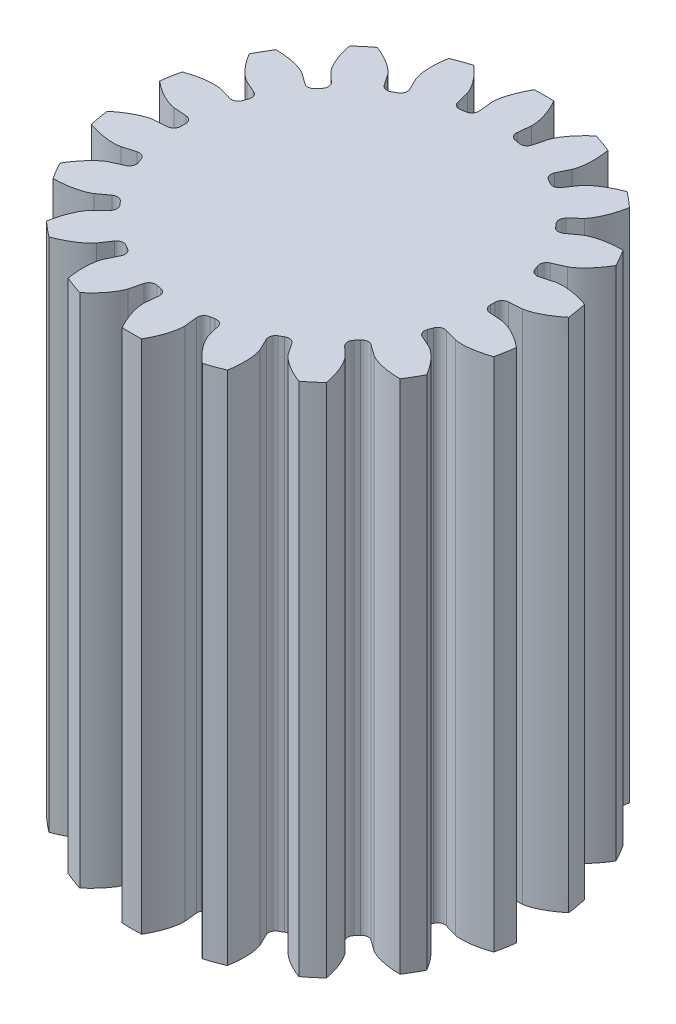
SolidWorks part; units mm, degrees
ref_plane "Front Plane" through (0, 0, 0) normal (0, 0, 1) x (1, 0, 0)
ref_plane "Top Plane" through (0, 0, 0) normal (0, 1, 0) x (1, 0, 0)
ref_plane "Right Plane" through (0, 0, 0) normal (1, 0, 0) x (0, 0, -1)
ref_axis "Axis" through (0, -13.75, 0) along (0, 1, 0)
sketch "Sketch1" plane through (0, 0, 0) normal (0, 1, 0) x (1, 0, 0)
  circle A0 centre (0, 0) radius 10
  dimension "D1" = 20
extrude "Gear Boss" add sketch "Sketch1" along normal mid plane 25
sketch "Sketch2" plane through (0, 0, 0) normal (0, 1, 0) x (1, 0, 0)
  line L0 (0, 0) -> (10, 0) construction
  line L1 (8.4425, 0.4988) -> (7.8104, 0.453)
  line L2 (9.9193, 1.2676) -> (9.9193, 0) construction
  line L3 (7.8104, -0.453) -> (8.4425, -0.4988)
  line L4 (8.4425, -0.4988) -> (8.4425, 0.4988) construction
  line L5 (9.9193, 0) -> (9.9193, -1.2676) construction
  circle A0 centre (0, 0) radius 8.4572 construction
  circle A1 centre (0, 0) radius 10 construction
  circle A4 centre (0, 0) radius 10
  arc A5 (7.4991, -0.1133) -> (7.4991, 0.1133) centre (0, 0) ccw
  arc A6 (7.8104, -0.453) -> (7.4991, -0.1133) centre (7.8346, -0.1184) cw
  arc A7 (7.8104, 0.453) -> (7.4991, 0.1133) centre (7.8346, 0.1184) ccw
  spline S0 degree 4 poles (8.4425, 0.4988) (8.445, 0.499) (8.452, 0.4996) (8.4734, 0.5021) (8.5155, 0.509) (8.5672, 0.5201) (8.6262, 0.5355) (8.6828, 0.5523) (8.7311, 0.5679) (8.7789, 0.5846) (8.8264, 0.6022) (8.8836, 0.6248) (8.9519, 0.6536) (9.0311, 0.6897) (9.1202, 0.7335) (9.2101, 0.7811) (9.2979, 0.8305) (9.3857, 0.8832) (9.47, 0.9363) (9.5567, 0.9942) (9.6362, 1.0492) (9.7241, 1.1139) (9.7947, 1.167) (9.8866, 1.2405) (9.9405, 1.2848) (10.0031, 1.3379) (10.0307, 1.3621) (10.0477, 1.3769) knots 0 0 0 0 0 0.005377 0.015084 0.04661 0.092111 0.119476 0.146842 0.174209 0.201575 0.228941 0.256307 0.307035 0.361767 0.4165 0.471232 0.525964 0.580697 0.635429 0.690161 0.744894 0.799626 0.854358 0.909091 0.954545 1 1 1 1 1 construction
  spline S1 degree 4 poles (8.4425, 0.4988) (8.445, 0.499) (8.452, 0.4996) (8.4734, 0.5021) (8.5155, 0.509) (8.5672, 0.5201) (8.6262, 0.5355) (8.6828, 0.5523) (8.7311, 0.5679) (8.7789, 0.5846) (8.8264, 0.6022) (8.8836, 0.6248) (8.9519, 0.6536) (9.0311, 0.6897) (9.1202, 0.7335) (9.2101, 0.7811) (9.2979, 0.8305) (9.3857, 0.8832) (9.47, 0.9363) (9.5567, 0.9942) (9.6362, 1.0492) (9.7241, 1.1139) (9.7947, 1.167) (9.8667, 1.2246) (9.9016, 1.2529) (9.9193, 1.2676) knots 0 0 0 0 0 0.005377 0.015084 0.04661 0.092111 0.119476 0.146842 0.174209 0.201575 0.228941 0.256307 0.307035 0.361767 0.4165 0.471232 0.525964 0.580697 0.635429 0.690161 0.744894 0.799626 0.854358 0.909091 0.909091 0.909091 0.909091 0.909091
  spline S2 degree 4 poles (8.4425, -0.4988) (8.445, -0.499) (8.452, -0.4996) (8.4734, -0.5021) (8.5155, -0.509) (8.5672, -0.5201) (8.6262, -0.5355) (8.6828, -0.5523) (8.7311, -0.5679) (8.7789, -0.5846) (8.8264, -0.6022) (8.8836, -0.6248) (8.9519, -0.6536) (9.0311, -0.6897) (9.1202, -0.7335) (9.2101, -0.7811) (9.2979, -0.8305) (9.3857, -0.8832) (9.47, -0.9363) (9.5567, -0.9942) (9.6362, -1.0492) (9.7241, -1.1139) (9.7947, -1.167) (9.8866, -1.2405) (9.9405, -1.2848) (10.0031, -1.3379) (10.0307, -1.3621) (10.0477, -1.3769) knots 0 0 0 0 0 0.005377 0.015084 0.04661 0.092111 0.119476 0.146842 0.174209 0.201575 0.228941 0.256307 0.307035 0.361767 0.4165 0.471232 0.525964 0.580697 0.635429 0.690161 0.744894 0.799626 0.854358 0.909091 0.954545 1 1 1 1 1 construction
  spline S3 degree 4 poles (8.4425, -0.4988) (8.445, -0.499) (8.452, -0.4996) (8.4734, -0.5021) (8.5155, -0.509) (8.5672, -0.5201) (8.6262, -0.5355) (8.6828, -0.5523) (8.7311, -0.5679) (8.7789, -0.5846) (8.8264, -0.6022) (8.8836, -0.6248) (8.9519, -0.6536) (9.0311, -0.6897) (9.1202, -0.7335) (9.2101, -0.7811) (9.2979, -0.8305) (9.3857, -0.8832) (9.47, -0.9363) (9.5567, -0.9942) (9.6362, -1.0492) (9.7241, -1.1139) (9.7947, -1.167) (9.8667, -1.2246) (9.9016, -1.2529) (9.9193, -1.2676) knots 0 0 0 0 0 0.005377 0.015084 0.04661 0.092111 0.119476 0.146842 0.174209 0.201575 0.228941 0.256307 0.307035 0.361767 0.4165 0.471232 0.525964 0.580697 0.635429 0.690161 0.744894 0.799626 0.854358 0.909091 0.909091 0.909091 0.909091 0.909091
  point P11 (8.439, 0.5553)
  point P19 (9.8851, 1.5118)
  dimension "D1" = 16.9145
  dimension "D3" = 20
  dimension "D6" = 7.5
  dimension "D2" = 0.3355
  dimension "D4" = 8.292
extrude "Tooth Cut" cut sketch "Sketch2" against normal through all both and the other way through all contours S3 S1 region at (9.0027, 0, 0)
pattern_circular "Tooth Pattern" count 18 over 360 about axis through (0, -13.75, 0) along (0, 1, 0) of "Tooth Cut"
equation "\"ringGearToothCount\" = 138"
equation "\"sunGearToothCount\" = 18"
equation "\"planetGearToothCount\" = (\"ringGearToothCount\" - \"sunGearToothCount\") / 2"
equation "\"faceWidth\" = 25mm"
equation "\"module\" = 1"
equation "\"pressureAngle\" = 20deg"
equation "\"toothCount\"= \"sunGearToothCount\""
equation "\"pitchAngle\" = 360deg / \"toothCount\""
equation "\"pitchDiameter\" = \"module\" * \"toothCount\""
equation "\"pitchRadius\" = \"pitchDiameter\" / 2"
equation "\"baseDiameter\" = \"pitchDiameter\" * cos(\"pressureAngle\")"
equation "\"baseRadius\" = \"baseDiameter\" / 2"
equation "\"addendum\" = 1.0 * \"module\""
equation "\"dedendum\" = 1.25 * \"module\""
equation "\"rootClearance\" = 0.25 * \"module\""
equation "\"addendumDiameter\" = \"pitchDiameter\" + 2 * \"addendum\""
equation "\"addendumRadius\" = \"addendumDiameter\" / 2"
equation "\"dedendumDiameter\" = \"pitchDiameter\" - 2 * \"dedendum\""
equation "\"dedendumRadius\" = \"dedendumDiameter\" / 2"
equation "\"rootDiameter\" = \"dedendumDiameter\" - 2 * \"rootClearance\""
equation "\"rootRadius\" = \"rootDiameter\" / 2"
equation "\"dedendumFilletRadius\" = \"rootClearance\" * cos(\"pressureAngle\") * tan((90 + \"pressureAngle\") / 2)"
equation "\"alpha\" = sqr(\"pitchDiameter\"^2 - \"baseDiameter\"^2) / \"baseDiameter\" * 180 / PI - \"pressureAngle\""
equation "\"beta\" = \"pitchAngle\" / 4 - \"alpha\""
equation "\"phi\" = sqr(\"addendumRadius\"^2 - \"baseRadius\"^2) / \"baseRadius\""
equation "\"betaR\" = \"beta\" * PI / 180"
equation "\"D1@Sketch1\"=\"addendumDiameter\""
equation "\"D1@Gear Boss\" = \"faceWidth\""
equation "\"D1@Sketch2\"=\"baseDiameter\""
equation "\"D1@Tooth Pattern\"=\"toothCount\""
equation "\"D3@Sketch2\"=\"addendumDiameter\""
equation "\"D6@Sketch2\"=\"rootRadius\""
equation "\"D2@Sketch2\"=\"dedendumFilletRadius\""
equation "\"D4@Sketch2\"=2*\"beta\""
